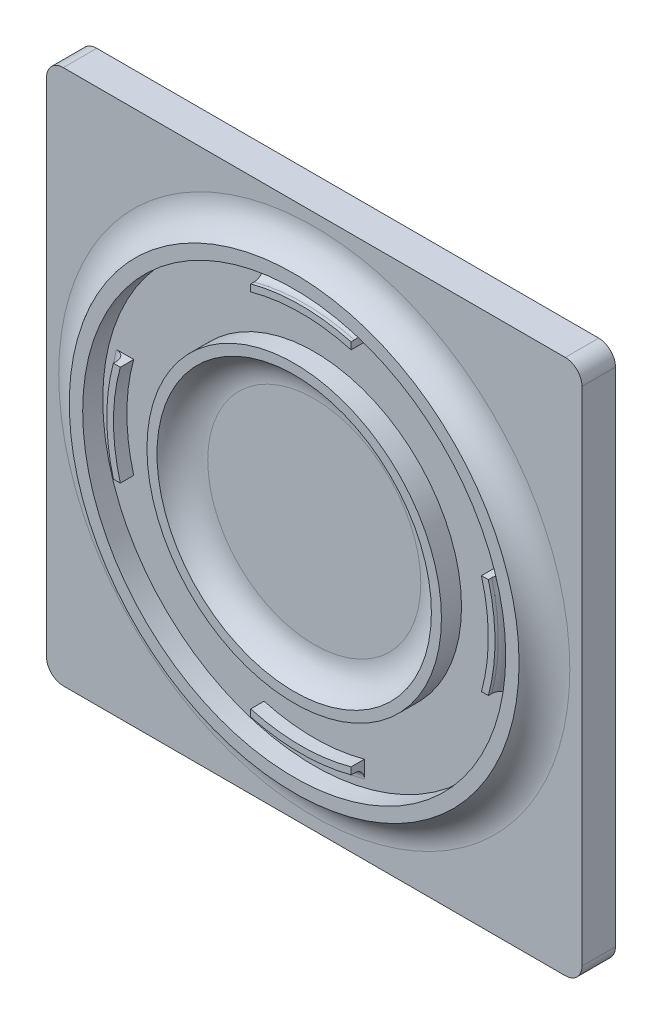
SolidWorks part; units mm, degrees
ref_plane "Front Plane" through (0, 0, 0) normal (0, 0, 1) x (1, 0, 0)
ref_plane "Top Plane" through (0, 0, 0) normal (0, 1, 0) x (1, 0, 0)
ref_plane "Right Plane" through (0, 0, 0) normal (1, 0, 0) x (0, 0, -1)
sketch "Sketch1" plane through (0, 0, 0) normal (0, 0, 1) x (1, 0, 0)
  line L1 (-40, 40) -> (40, 40)
  line L2 (-40, 40) -> (-40, -40)
  line L3 (-40, -40) -> (40, -40)
  line L4 (40, 40) -> (40, -40)
  line L5 (-40, 40) -> (40, -40) construction
  line L6 (-40, -40) -> (40, 40) construction
  point P0 (0, 0)
  dimension "D1" = 80
  dimension "D2" = 80
extrude "Boss-Extrude1" add sketch "Sketch1" along normal blind 5
fillet "Fillet1" radius 2.5 4 edges at (40, 40, 2.5) (-40, 40, 2.5) (40, -40, 2.5) (-40, -40, 2.5)
sketch "Sketch5" plane through (0, 0, 5) normal (0, 0, 1) x (1, 0, 0)
  line L6 (-7.5, 29) -> (7.5, 29)
  line L11 (-7.5, 29) -> (-7.5, -29)
  line L12 (-7.5, -29) -> (7.5, -29)
  line L16 (7.5, 29) -> (7.5, -29)
  line L17 (-7.5, 29) -> (7.5, -29) construction
  line L18 (-7.5, -29) -> (7.5, 29) construction
  line L19 (-29, 7.5) -> (29, 7.5)
  line L20 (-29, 7.5) -> (-29, -7.5)
  line L21 (-29, -7.5) -> (29, -7.5)
  line L22 (29, 7.5) -> (29, -7.5)
  line L23 (-29, 7.5) -> (29, -7.5) construction
  line L24 (-29, -7.5) -> (29, 7.5) construction
  circle A8 centre (0, 0) radius 28
  circle A9 centre (0, 0) radius 29
  dimension "D1" = 58
  dimension "D2" = 56
  dimension "D3" = 15
  dimension "D4" = 58
  dimension "D5" = 15
  dimension "D6" = 58
extrude "Boss-Extrude5" add sketch "Sketch5" along normal blind 2 contours L16 A9 L11 A8 | A9 L19 A8 L21 | L19 A9 L21 A8 | L11 A9 L16 A8 region at (0, 28.1642, 5) region at (-28.1642, 0, 5) region at (28.1642, 0, 5) region at (0, -28.1642, 5)
sketch "Sketch12" plane through (0, 0, 5) normal (0, 0, 1) x (1, 0, 0)
  circle A0 centre (0, 0) radius 31.6
  circle A1 centre (0, 0) radius 33.6
  dimension "D1" = 63.2
  dimension "D2" = 67.2
extrude "Boss-Extrude8" add sketch "Sketch12" along normal blind 3
sketch "Sketch13" plane through (0, 0, 5) normal (0, 0, 1) x (1, 0, 0)
  circle A0 centre (0, 0) radius 20.5
  circle A1 centre (0, 0) radius 22
  dimension "D1" = 44
  dimension "D2" = 41
extrude "Boss-Extrude9" add sketch "Sketch13" along normal blind 3
fillet "Fillet2" radius 1.5 4 edges at (29, 0, 5) (0, -29, 5) (-29, 0, 5) (0, 29, 5)
fillet "Fillet3" radius 5 2 edges at (33.6, 0, 5) (20.5, 0, 5)
